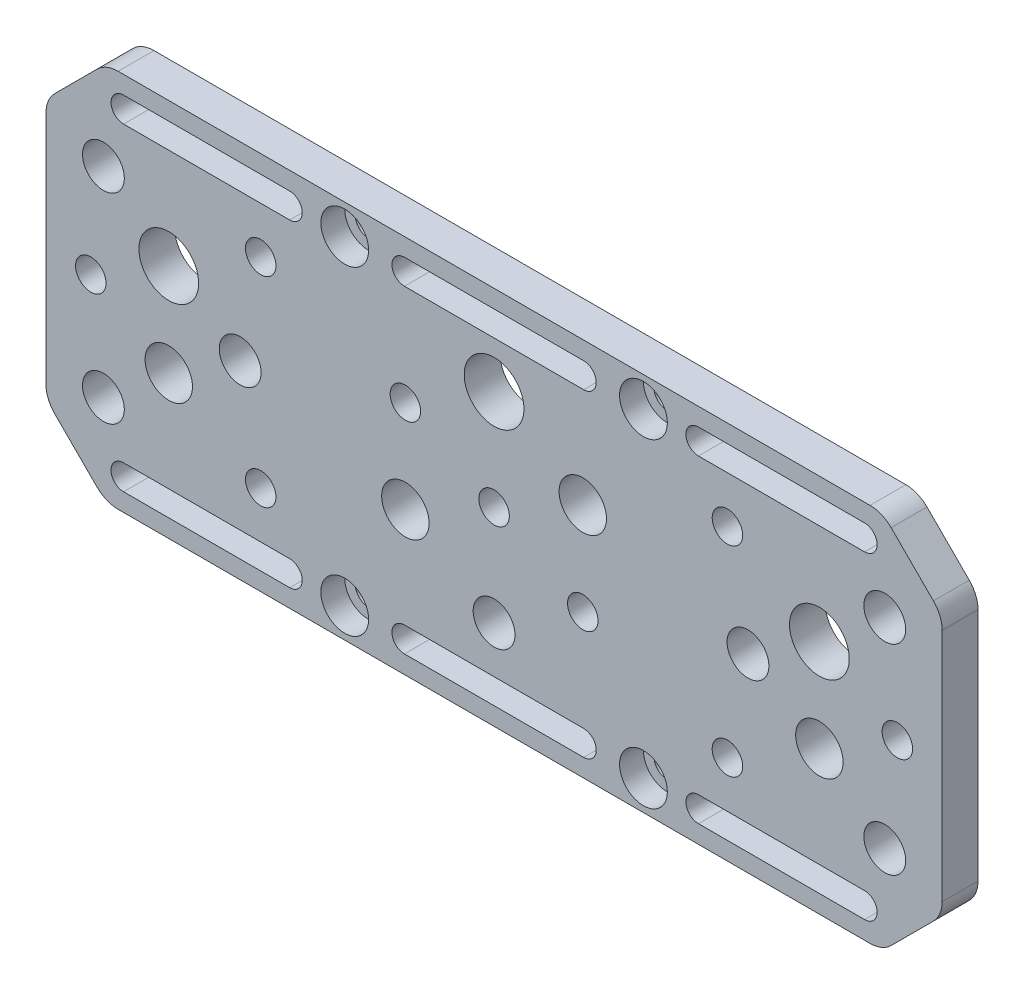
SolidWorks part; units mm, degrees
material "Сплав 2024"
ref_plane "Спереди" through (0, 0, 0) normal (0, 0, 1) x (1, 0, 0)
ref_plane "Сверху" through (0, 0, 0) normal (0, 1, 0) x (1, 0, 0)
ref_plane "Справа" through (0, 0, 0) normal (1, 0, 0) x (0, 0, -1)
sketch "Эскиз5" plane through (0, 0, 0) normal (0, 0, 1) x (1, 0, 0)
  line L0 (-75, 21.75) -> (-65, 31.75)
  line L1 (-65, 31.75) -> (65, 31.75)
  line L2 (-75, 21.75) -> (-75, -21.75)
  line L3 (-65, -31.75) -> (65, -31.75)
  line L4 (75, 21.75) -> (75, -21.75)
  line L5 (-75, 31.75) -> (75, -31.75) construction
  line L6 (-75, -31.75) -> (75, 31.75) construction
  line L7 (-75, -21.75) -> (-65, -31.75)
  line L8 (65, -31.75) -> (75, -21.75)
  line L9 (65, 31.75) -> (75, 21.75)
  point P0 (0, 0)
  dimension "D1" = 150
  dimension "D2" = 63.5
extrude "Бобышка-Вытянуть2" add sketch "Эскиз5" along normal blind 6
sketch "Эскиз6" plane through (0, 0, 6) normal (0, 0, 1) x (1, 0, 0)
  line L0 (-25, 31.75) -> (-25, -31.75) construction
  line L1 (65, 31.75) -> (-65, 31.75) construction
  line L2 (-65, -31.75) -> (65, -31.75) construction
  line L3 (25, 31.75) -> (25, -31.75) construction
  line L4 (-75, 21.75) -> (-75, -21.75) construction
  line L5 (75, -21.75) -> (75, 21.75) construction
  line L6 (-75, 26.75) -> (75, 26.75) construction
  line L7 (75, -26.75) -> (-75, -26.75) construction
  dimension "D1" = 50
  dimension "D2" = 50
  dimension "D3" = 5
  dimension "D4" = 5
hole_wizard "Цековка для винта с внутренним шестигранником M41" positions "Эскиз8" profile "Эскиз7" counterbore size "M4" standard "Ansi Metric" end condition through all
sketch "Эскиз8" plane through (0, 0, 6) normal (0, 0, 1) x (1, 0, 0)
  line L0 (-25, 31.75) -> (-25, -31.75) construction
  line L1 (-75, 26.75) -> (75, 26.75) construction
  line L2 (75, -26.75) -> (-75, -26.75) construction
  line L3 (25, 31.75) -> (25, -31.75) construction
  point P0 (-25, 26.75)
  point P6 (-25, -26.75)
  point P10 (25, -26.75)
  point P14 (25, 26.75)
sketch "Эскиз7" plane through (-25, 26.75, 6) normal (1, 0, 0) x (0, -1, 0)
  line L0 (0, 0) -> (0, 6)
  line L1 (0, 6) -> (2.25, 6)
  line L3 (2.25, 6) -> (2.25, 4)
  line L4 (2.25, 4) -> (4, 4)
  line L5 (4, 4) -> (4, 0)
  line L7 (4, 0) -> (0, 0)
  line L11 (0, -6.35) -> (0, 107.95) construction
  dimension "Диаметр сквозного отверстия" = 4.5
  dimension "Глубина сквозного отверстия" = 6
  dimension "Диаметр цековки" = 8
  dimension "Глубина цековки" = 4
sketch "Эскиз13" plane through (0, 0, 6) normal (0, 0, 1) x (1, 0, 0)
  line L0 (-34.2079, 26.65) -> (-62.0163, 26.65) construction
  line L1 (-34.2079, 24.55) -> (-62.0163, 24.55)
  line L2 (-34.2079, 28.75) -> (-62.0163, 28.75)
  line L3 (34.2079, 26.65) -> (62.0163, 26.65) construction
  line L4 (34.2079, 24.55) -> (62.0163, 24.55)
  line L5 (34.2079, 28.75) -> (62.0163, 28.75)
  line L6 (-34.2079, -26.65) -> (-62.0163, -26.65) construction
  line L7 (-34.2079, -24.55) -> (-62.0163, -24.55)
  line L8 (-34.2079, -28.75) -> (-62.0163, -28.75)
  line L9 (34.2079, -26.65) -> (62.0163, -26.65) construction
  line L10 (34.2079, -24.55) -> (62.0163, -24.55)
  line L11 (-75, 0) -> (75, 0) construction
  line L12 (-75, 21.75) -> (-75, -21.75) construction
  line L13 (75, -21.75) -> (75, 21.75) construction
  line L14 (-75, 7.75) -> (75, 7.75) construction
  line L15 (-75, 16.75) -> (75, 16.75) construction
  line L16 (65, 31.75) -> (-65, 31.75) construction
  line L17 (-75, -7.75) -> (75, -7.75) construction
  line L18 (-75, -16.75) -> (75, -16.75) construction
  line L19 (0, 31.75) -> (0, -31.75) construction
  line L20 (-65, -31.75) -> (65, -31.75) construction
  line L21 (34.2079, -28.75) -> (62.0163, -28.75)
  line L22 (-15, 26.65) -> (15, 26.65) construction
  line L23 (-15, 28.75) -> (15, 28.75)
  line L24 (-15, 24.55) -> (15, 24.55)
  line L25 (-15, -26.65) -> (15, -26.65) construction
  line L26 (-15, -28.75) -> (15, -28.75)
  line L27 (-15, -24.55) -> (15, -24.55)
  line L28 (-16.75, 16.75) -> (-16.75, -16.75) construction
  line L29 (16.75, 16.75) -> (16.75, -16.75) construction
  arc A0 (-15, 28.75) -> (-15, 24.55) centre (-15, 26.65) ccw
  circle A1 centre (0, 0) radius 67.5 construction
  circle A2 centre (0, 0) radius 55 construction
  circle A3 centre (0, 0) radius 42.5 construction
  circle A4 centre (-54.4512, 7.75) radius 5
  circle A5 centre (-65.3887, 16.75) radius 3.5
  arc A6 (15, 24.55) -> (15, 28.75) centre (15, 26.65) ccw
  circle A7 centre (-65.3887, -16.75) radius 3.5
  circle A8 centre (65.3887, -16.75) radius 3.5
  arc A9 (-15, -28.75) -> (-15, -24.55) centre (-15, -26.65) cw
  arc A10 (15, -24.55) -> (15, -28.75) centre (15, -26.65) cw
  circle A11 centre (54.4512, 7.75) radius 5
  circle A12 centre (65.3887, 16.75) radius 3.5
  circle A13 centre (0, 0) radius 16.75 construction
  circle A14 centre (0, -16.75) radius 3.5
  circle A15 centre (-42.5, 0) radius 3.5
  circle A16 centre (0, 16.75) radius 5
  circle A20 centre (42.5, 0) radius 3.5
  arc A23 (-34.2079, 24.55) -> (-34.2079, 28.75) centre (-34.2079, 26.65) ccw
  arc A24 (-62.0163, 28.75) -> (-62.0163, 24.55) centre (-62.0163, 26.65) ccw
  arc A25 (34.2079, 24.55) -> (34.2079, 28.75) centre (34.2079, 26.65) cw
  arc A26 (62.0163, 28.75) -> (62.0163, 24.55) centre (62.0163, 26.65) cw
  arc A27 (-34.2079, -24.55) -> (-34.2079, -28.75) centre (-34.2079, -26.65) cw
  arc A28 (-62.0163, -28.75) -> (-62.0163, -24.55) centre (-62.0163, -26.65) cw
  arc A29 (34.2079, -24.55) -> (34.2079, -28.75) centre (34.2079, -26.65) ccw
  arc A30 (62.0163, -28.75) -> (62.0163, -24.55) centre (62.0163, -26.65) ccw
  point P2 (0, 26.65)
  point P46 (0, -26.65)
  point P67 (-48.1121, 26.65)
  point P74 (48.1121, 26.65)
  point P81 (-48.1121, -26.65)
  point P88 (48.1121, -26.65)
  dimension "D1" = 135
  dimension "D2" = 15
  dimension "D3" = 9
  dimension "D4" = 110
  dimension "D5" = 85
  dimension "D6" = 2.1
  dimension "D7" = 10
  dimension "D8" = 7
  dimension "D9" = 30
  dimension "D10" = 7
  dimension "D11" = 7
  dimension "D12" = 10
  dimension "D13" = 7
  dimension "D16" = 2.1
  dimension "D17" = 3
extrude "Вырез-Вытянуть1" cut sketch "Эскиз13" against normal through all
fillet "Скругление1" radius 5 8 edges at (65, 31.75, 3) (75, 21.75, 3) (75, -21.75, 3) (65, -31.75, 3) (-65, -31.75, 3) (-75, -21.75, 3) (-75, 21.75, 3) (-65, 31.75, 3)
hole_wizard "Отверстие обработанное метчиком 1/4-202" positions "Эскиз18" profile "Эскиз17" tap size "1/4-20" standard "Ansi Inch" end condition through all
sketch "Эскиз18" plane through (0, 0, 6) normal (0, 0, 1) x (1, 0, 0)
  line L0 (-75, 0) -> (75, 0) construction
  line L1 (-75, 16.75) -> (75, 16.75) construction
  line L2 (-75, -16.75) -> (75, -16.75) construction
  circle A0 centre (0, 0) radius 67.5 construction
  circle A1 centre (0, 0) radius 42.5 construction
  point P0 (-67.5, 0)
  point P6 (-39.06, 16.75)
  point P12 (-39.06, -16.75)
  point P16 (39.06, 16.75)
  point P18 (39.06, -16.75)
  point P20 (67.5, 0)
sketch "Эскиз17" plane through (-67.5, 0, 6) normal (1, 0, 0) x (0, -1, 0)
  line L0 (0, 0) -> (0, 6)
  line L1 (0, 6) -> (2.5527, 6)
  line L2 (2.5527, 6) -> (2.5527, 0)
  line L5 (2.5527, 0) -> (0, 0)
  line L11 (0, -6.35) -> (0, 107.95) construction
  dimension "Диаметр проходного сверла" = 5.1054
  dimension "Глубина проходного сверла" = 6
cosmetic thread "Отверстие резьбы11" parameters "D2"=6.35
cosmetic thread "Отверстие резьбы12" parameters "D2"=6.35
cosmetic thread "Отверстие резьбы13" parameters "D2"=6.35
cosmetic thread "Отверстие резьбы14" parameters "D2"=6.35
cosmetic thread "Отверстие резьбы15" parameters "D2"=6.35
cosmetic thread "Отверстие резьбы16" parameters "D2"=6.35
hole_wizard "Отверстие обработанное метчиком 3/8-161" positions "Эскиз20" profile "Эскиз19" tap size "3/8-16" standard "Ansi Inch" end condition through all
sketch "Эскиз20" plane through (0, 0, 6) normal (0, 0, 1) x (1, 0, 0)
  line L0 (-75, -7.75) -> (75, -7.75) construction
  circle A0 centre (0, 0) radius 55 construction
  point P0 (-54.4512, -7.75)
  point P6 (54.4512, -7.75)
sketch "Эскиз19" plane through (-54.4512, -7.75, 6) normal (1, 0, 0) x (0, -1, 0)
  line L0 (0, 0) -> (0, 6)
  line L1 (0, 6) -> (3.9687, 6)
  line L2 (3.9687, 6) -> (3.9687, 0)
  line L5 (3.9687, 0) -> (0, 0)
  line L11 (0, -6.35) -> (0, 107.95) construction
  dimension "Диаметр проходного сверла" = 7.9375
  dimension "Глубина проходного сверла" = 6
cosmetic thread "Отверстие резьбы17" parameters "D2"=9.525
cosmetic thread "Отверстие резьбы18" parameters "D2"=9.525
hole_wizard "Отверстие обработанное метчиком 1/4-203" positions "Эскиз22" profile "Эскиз21" tap size "1/4-20" standard "Ansi Inch" end condition through all
sketch "Эскиз22" plane through (0, 0, 6) normal (0, 0, 1) x (1, 0, 0)
  line L0 (-75, 7.75) -> (75, 7.75) construction
  line L1 (-75, -7.75) -> (75, -7.75) construction
  circle A0 centre (0, 0) radius 16.75 construction
  point P0 (0, 0)
  point P48 (-14.8492, 7.75)
  point P54 (14.8492, -7.75)
sketch "Эскиз21" plane through (0, 0, 6) normal (1, 0, 0) x (0, -1, 0)
  line L0 (0, 0) -> (0, 6)
  line L1 (0, 6) -> (2.5527, 6)
  line L2 (2.5527, 6) -> (2.5527, 0)
  line L5 (2.5527, 0) -> (0, 0)
  line L11 (0, -6.35) -> (0, 107.95) construction
  dimension "Диаметр проходного сверла" = 5.1054
  dimension "Глубина проходного сверла" = 6
cosmetic thread "Отверстие резьбы19" parameters "D2"=6.35
cosmetic thread "Отверстие резьбы20" parameters "D2"=6.35
cosmetic thread "Отверстие резьбы23" parameters "D2"=6.35
hole_wizard "Отверстие обработанное метчиком 3/8-163" positions "Эскиз28" profile "Эскиз27" tap size "3/8-16" standard "Ansi Inch" end condition through all
sketch "Эскиз28" plane through (0, 0, 6) normal (0, 0, 1) x (1, 0, 0)
  line L0 (-75, -7.75) -> (75, -7.75) construction
  line L1 (-75, 7.75) -> (75, 7.75) construction
  circle A0 centre (0, 0) radius 16.75 construction
  point P0 (-14.8492, -7.75)
  point P6 (14.8492, 7.75)
sketch "Эскиз27" plane through (-14.8492, -7.75, 6) normal (1, 0, 0) x (0, -1, 0)
  line L0 (0, 0) -> (0, 6)
  line L1 (0, 6) -> (3.9687, 6)
  line L2 (3.9687, 6) -> (3.9687, 0)
  line L5 (3.9687, 0) -> (0, 0)
  line L11 (0, -6.35) -> (0, 107.95) construction
  dimension "Диаметр проходного сверла" = 7.9375
  dimension "Глубина проходного сверла" = 6
cosmetic thread "Отверстие резьбы25" parameters "D2"=9.525
cosmetic thread "Отверстие резьбы26" parameters "D2"=9.525
fillet "Скругление2" [suppressed] radius 0.5
sketch "Эскиз29" plane through (0, 0, 0) normal (0, 0, 1) x (1, 0, 0)
  line L0 (-75, 19.6789) -> (-75, -19.6789) construction
  line L1 (-62.9289, -31.75) -> (62.9289, -31.75) construction
  point P0 (-75, -31.75)
